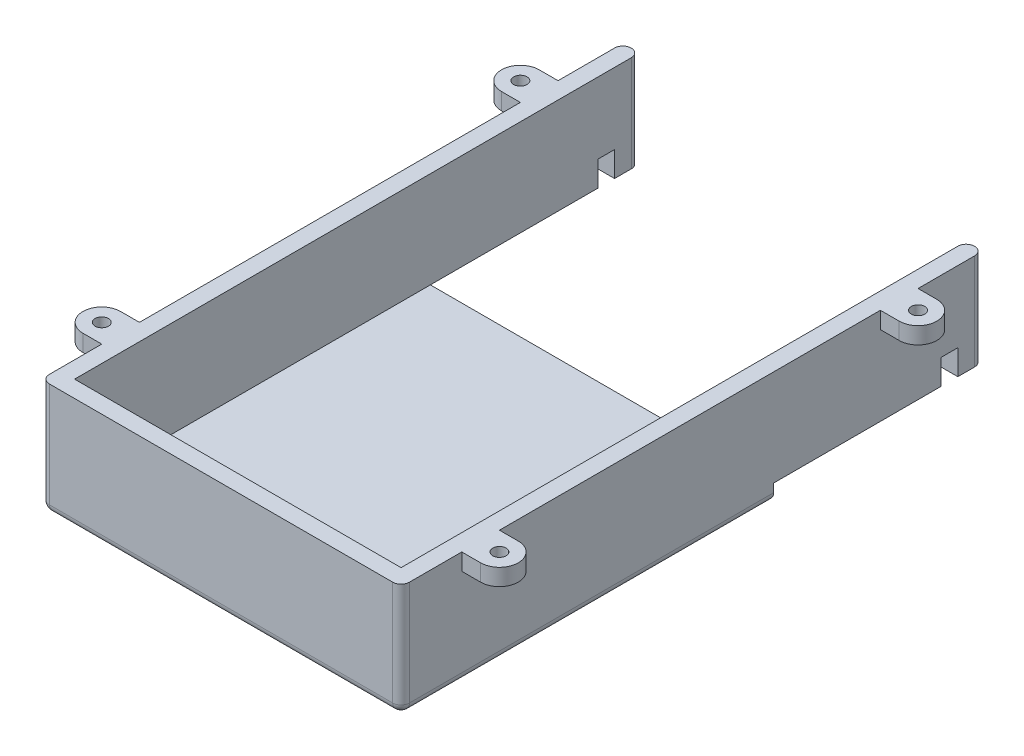
SolidWorks part; units mm, degrees
ref_plane "Front Plane" through (0, 0, 0) normal (0, 0, 1) x (1, 0, 0)
ref_plane "Top Plane" through (0, 0, 0) normal (0, 1, 0) x (1, 0, 0)
ref_plane "Right Plane" through (0, 0, 0) normal (1, 0, 0) x (0, 0, -1)
sketch "Sketch2" plane through (0, 0, 0) normal (0, 1, 0) x (1, 0, 0)
  line L0 (-45.9562, 28.6427) -> (-45.9562, -110.3573)
  line L1 (36.0438, 28.6427) -> (40.0438, 28.6427)
  line L2 (-41.9562, 28.6427) -> (-41.9562, -106.3573)
  line L3 (-41.9562, -106.3573) -> (36.0438, -106.3573)
  line L4 (36.0438, 28.6427) -> (36.0438, -106.3573)
  line L5 (-45.9562, -110.3573) -> (40.0438, -110.3573)
  line L6 (40.0438, 28.6427) -> (40.0438, -110.3573)
  line L7 (-45.9562, 28.6427) -> (-41.9562, 28.6427)
  dimension "D1" = 78
  dimension "D2" = 135
  dimension "D3" = 4
  dimension "D5" = 4
  dimension "D6" = 4
  dimension "D7" = 135
extrude "Boss-Extrude3" add sketch "Sketch2" along normal blind 23
sketch "Sketch5" plane through (0, 0, 0) normal (0, -1, 0) x (1, 0, 0)
  line L0 (40.0438, 110.3573) -> (40.0438, -28.6427) construction
  line L1 (40.0438, 21.3573) -> (-45.9562, 21.3573)
  line L2 (40.0438, 21.3573) -> (40.0438, 110.3573)
  line L3 (40.0438, 110.3573) -> (-45.9562, 110.3573)
  line L4 (-45.9562, 21.3573) -> (-45.9562, 110.3573)
  line L5 (40.0438, -28.6427) -> (36.0438, -28.6427) construction
  point P6 (40.0438, -17.5312)
  dimension "D1" = 50
extrude "Boss-Extrude4" add sketch "Sketch5" along normal blind 4
sketch "Sketch7" plane through (0, 0, 0) normal (0, -1, 0) x (1, 0, 0)
  line L1 (40.0438, -18.6427) -> (-45.9562, -18.6427)
  line L2 (40.0438, -18.6427) -> (40.0438, -22.6427)
  line L3 (40.0438, -22.6427) -> (-45.9562, -22.6427)
  line L4 (-45.9562, -18.6427) -> (-45.9562, -22.6427)
  line L6 (40.0438, 21.3573) -> (40.0438, -28.6427) construction
  line L7 (40.0438, -28.6427) -> (36.0438, -28.6427) construction
  point P10 (-51.3244, -30.3299)
  point P11 (-32.9488, -24.8881)
  dimension "D1" = 4
  dimension "D2" = 6
extrude "Cut-Extrude2" cut sketch "Sketch7" against normal blind 6
fillet "Fillet2" radius 2 3 edges at (-45.9562, -4, 65.8573) (-2.9562, -4, 110.3573) (40.0438, -4, 65.8573)
fillet "Fillet3" radius 2 6 edges at (39.458, -3.4142, 109.7716) (-45.3704, -3.4142, 109.7716) (-41.9562, 11.5, -28.6427) (40.0438, 10.5, 110.3573) (-45.9562, 10.5, 110.3573) (-45.9562, 11.5, -28.6427)
sketch "Sketch8" plane through (0, 23, 0) normal (0, 1, 0) x (1, 0, 0)
  line L0 (40.0438, -95.8573) -> (40.0438, -86.8573)
  line L1 (-41.9562, -91.3573) -> (36.0438, -91.3573) construction
  line L2 (-41.9562, -106.3573) -> (-41.9562, 26.6427) construction
  line L3 (36.0438, -21.3573) -> (36.0438, -106.3573) construction
  line L4 (-50.4562, -91.3573) -> (44.5438, -91.3573) construction
  line L5 (36.0438, -106.3573) -> (-41.9562, -106.3573) construction
  line L6 (-50.4562, 13.1427) -> (-45.9562, 13.1427)
  line L7 (-45.9562, 26.6427) -> (-45.9562, -108.3573) construction
  line L8 (-50.4562, 4.1427) -> (-45.9562, 4.1427)
  line L9 (44.5438, 13.1427) -> (40.0438, 13.1427)
  line L10 (40.0438, -108.3573) -> (40.0438, 28.6427) construction
  line L11 (44.5438, 4.1427) -> (40.0438, 4.1427)
  line L12 (44.5438, -86.8573) -> (40.0438, -86.8573)
  line L13 (44.5438, -95.8573) -> (40.0438, -95.8573)
  line L14 (-50.4562, -86.8573) -> (-45.9562, -86.8573)
  line L15 (-50.4562, -95.8573) -> (-45.9562, -95.8573)
  line L16 (40.0438, 4.1427) -> (40.0438, 13.1427)
  line L17 (-45.9562, 13.1427) -> (-45.9562, 4.1427)
  line L18 (-45.9562, -86.8573) -> (-45.9562, -95.8573)
  circle A0 centre (-50.4562, 8.6427) radius 1.6
  circle A1 centre (-50.4562, -91.3573) radius 1.6
  circle A2 centre (44.5438, 8.6427) radius 1.6
  circle A3 centre (44.5438, -91.3573) radius 1.6
  arc A4 (-50.4562, -86.8573) -> (-50.4562, -95.8573) centre (-50.4562, -91.3573) ccw
  arc A5 (44.5438, -95.8573) -> (44.5438, -86.8573) centre (44.5438, -91.3573) ccw
  arc A6 (44.5438, 4.1427) -> (44.5438, 13.1427) centre (44.5438, 8.6427) ccw
  arc A7 (-50.4562, 13.1427) -> (-50.4562, 4.1427) centre (-50.4562, 8.6427) ccw
  point P8 (-2.9562, -91.3573)
  point P9 (-2.9562, -91.3573)
  dimension "D3" = 3.2
  dimension "D4" = 15
  dimension "D1" = 95
  dimension "D2" = 100
extrude "Boss-Extrude5" add sketch "Sketch8" against normal blind 4
fillet "Fillet4" radius 2 2 edges at (40.0438, 11.5, -28.6427) (36.0438, 11.5, -28.6427)
